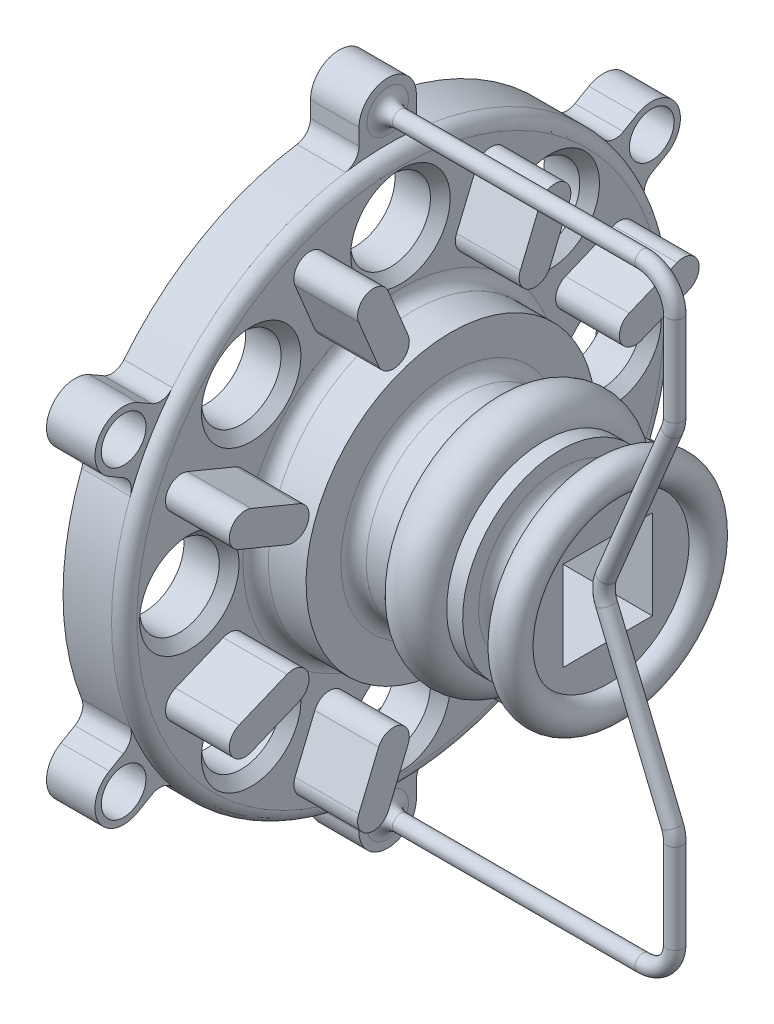
SolidWorks part; units mm, degrees
material "1060 Alloy"
ref_plane "Front Plane" through (0, 0, 0) normal (0, 0, 1) x (1, 0, 0)
ref_plane "Top Plane" through (0, 0, 0) normal (0, 1, 0) x (1, 0, 0)
ref_plane "Right Plane" through (0, 0, 0) normal (1, 0, 0) x (0, 0, -1)
sketch "Sketch1" plane through (0, 0, 0) normal (0, 0, 1) x (1, 0, 0)
  line L0 (0, 24.511) -> (0, 28.829)
  line L1 (0, 28.829) -> (10.033, 28.829)
  line L2 (10.033, 28.829) -> (10.033, 19.3675)
  line L3 (10.033, 19.3675) -> (18.415, 19.3675)
  line L4 (31.75, 19.3675) -> (31.75, 16.1925)
  line L6 (38.1, 16.1925) -> (38.1, 19.3675)
  line L7 (41.275, 16.1925) -> (41.275, 0)
  line L8 (41.275, 0) -> (3.937, 0)
  line L9 (28.575, 19.3675) -> (31.75, 19.3675)
  line L10 (0, 24.511) -> (3.937, 24.511)
  line L11 (3.937, 24.511) -> (3.937, 0)
  line L12 (0, 0) -> (3.937, 0)
  arc A0 (41.275, 16.1925) -> (38.1, 19.3675) centre (41.275, 19.3675) ccw
  arc A1 (31.75, 16.1925) -> (38.1, 16.1925) centre (34.925, 16.1925) ccw
  arc A2 (28.575, 19.3675) -> (18.415, 19.3675) centre (23.495, 19.3675) ccw
  dimension "D1" = 3.175
  dimension "D2" = 41.275
  dimension "D3" = 3.175
  dimension "D7" = 10.16
  dimension "D4" = 6.35
  dimension "D5" = 16.1925
  dimension "D6" = 19.3675
  dimension "D8" = 11.43
  dimension "D9" = 10.033
  dimension "D10" = 28.829
  dimension "D11" = 3.937
  dimension "D12" = 24.511
revolve "Revolve1" add sketch "Sketch1" angle 360 about L8
sketch "Sketch2" plane through (3.937, 0, 0) normal (-1, 0, 0) x (0, 0, 1)
  line L1 (-8.89, 8.89) -> (8.89, 8.89)
  line L2 (-8.89, 8.89) -> (-8.89, -8.89)
  line L3 (-8.89, -8.89) -> (8.89, -8.89)
  line L4 (8.89, 8.89) -> (8.89, -8.89)
  line L5 (-8.89, 8.89) -> (8.89, -8.89) construction
  line L6 (-8.89, -8.89) -> (8.89, 8.89) construction
  point P0 (0, 0)
  dimension "D1" = 17.78
  dimension "D2" = 17.78
extrude "Cut-Extrude2" cut sketch "Sketch2" against normal up to next
sketch "Sketch3" plane through (0, 0, 0) normal (-1, 0, 0) x (0, 0, 1)
  circle A0 centre (0, 0) radius 54.991
  circle A2 centre (0, 0) radius 24.511 construction
  circle A3 centre (0, 0) radius 24.511
  dimension "D1" = 109.982
extrude "Boss-Extrude1" add sketch "Sketch3" along normal blind 12.192
sketch "Sketch5" plane through (-12.192, 0, 0) normal (-1, 0, 0) x (0, 0, 1)
  circle A0 centre (0, 0) radius 51.816
  dimension "D1" = 103.632
extrude "Cut-Extrude4" cut sketch "Sketch5" against normal blind 3.175
chamfer "Chamfer1" distance 6.35 angle 45 1 edges at (-9.017, -24.511, 0)
sketch "Sketch4" plane through (0, 0, 0) normal (1, 0, 0) x (0, 0, -1)
  line L0 (0, 0) -> (54.991, 0) construction
  line L2 (0, 0) -> (29.7246, 29.7246) construction
  circle A0 centre (0, 0) radius 54.991 construction
  circle A1 centre (0, 0) radius 42.037 construction
  circle A2 centre (29.7246, 29.7246) radius 7.9375
  dimension "D3" = 84.074
  dimension "D6" = 15.875
  dimension "D2" = 45
extrude "Cut-Extrude3" cut sketch "Sketch4" against normal up to next
sketch "Sketch6" plane through (0, 0, 0) normal (1, 0, 0) x (0, 0, -1)
  line L0 (0, 0) -> (38.8371, 16.0869) construction
  line L1 (0, 0) -> (42.037, 0) construction
  line L2 (34.0734, 14.1137) -> (43.6008, 18.0601) construction
  line L3 (32.8584, 17.047) -> (42.3858, 20.9934)
  line L4 (35.2884, 11.1804) -> (44.8159, 15.1267)
  circle A0 centre (0, 0) radius 42.037 construction
  arc A1 (32.8584, 17.047) -> (35.2884, 11.1804) centre (34.0734, 14.1137) ccw
  arc A2 (44.8159, 15.1267) -> (42.3858, 20.9934) centre (43.6008, 18.0601) ccw
  point P3 (38.8371, 16.0869)
  dimension "D1" = 84.074
  dimension "D4" = 3.175
  dimension "D2" = 22.5
  dimension "D3" = 5.1562
extrude "Boss-Extrude2" add sketch "Sketch6" along normal blind 12.7
chamfer "Chamfer2" distance 1.9685 angle 45 1 edges at (0, 37.6621, -29.7246)
pattern_circular "CirPattern1" count 8 over 360 about axis through (41.275, 0, 0) along (1, 0, 0) of "Cut-Extrude3", "Boss-Extrude2", "Chamfer2"
sketch "Sketch7" plane through (-12.192, 0, 0) normal (-1, 0, 0) x (0, 0, 1)
  line L0 (5.715, 60.706) -> (5.715, 54.6932)
  line L1 (-5.715, 60.706) -> (-5.715, 54.6932)
  line L2 (0, 60.706) -> (0, 0) construction
  arc A0 (5.715, 60.706) -> (-5.715, 60.706) centre (0, 60.706) ccw
  circle A1 centre (0, 0) radius 54.991 construction
  arc A2 (5.715, 54.6932) -> (-5.715, 54.6932) centre (0, 0) ccw
  dimension "D1" = 60.706
  dimension "D2" = 11.43
  dimension "D3" = 6.0128
extrude "Boss-Extrude3" add sketch "Sketch7" against normal blind 9.652
fillet "Fillet1" radius 3.175 2 edges at (-7.366, 54.6932, -5.715) (-7.366, 54.6932, 5.715)
pattern_circular "CirPattern2" count 6 over 360 about axis through (-12.192, 0, 0) along (1, 0, 0) of "Boss-Extrude3", "Fillet1"
sketch "Sketch8" plane through (-12.192, 0, 0) normal (-1, 0, 0) x (0, 0, 1)
  circle A0 centre (52.5729, 30.353) radius 4.445
  circle A1 centre (52.5729, -30.353) radius 4.445
  circle A2 centre (-52.5729, -30.353) radius 4.445
  circle A3 centre (-52.5729, 30.353) radius 4.445
  dimension "D1" = 8.89
extrude "Cut-Extrude5" cut sketch "Sketch8" against normal blind 9.652
sketch "Sketch9" plane through (0, 0, 0) normal (0, 0, 1) x (1, 0, 0)
  line L0 (-2.54, 60.706) -> (48.26, 60.706)
  line L1 (54.61, 54.356) -> (54.61, 36.5676)
  line L2 (54.1278, 34.1402) -> (41.0091, 2.4273)
  line L3 (41.0091, -2.4273) -> (54.1278, -34.1402)
  line L4 (54.61, -36.5676) -> (54.61, -54.356)
  line L5 (48.26, -60.706) -> (-2.54, -60.706)
  line L6 (-12.192, 66.421) -> (-12.192, 60.706) construction
  line L7 (0, 0) -> (40.005, 0) construction
  arc A0 (54.61, 36.5676) -> (54.1278, 34.1402) centre (48.26, 36.5676) cw
  arc A1 (54.1278, -34.1402) -> (54.61, -36.5676) centre (48.26, -36.5676) cw
  arc A2 (41.0091, 2.4273) -> (41.0091, -2.4273) centre (46.8769, 0) ccw
  arc A3 (54.61, -54.356) -> (48.26, -60.706) centre (48.26, -54.356) cw
  arc A4 (48.26, 60.706) -> (54.61, 54.356) centre (48.26, 54.356) cw
  point P15 (54.61, 35.306)
  point P18 (54.61, -35.306)
  point P24 (54.61, -60.706)
  point P27 (54.61, 60.706)
  dimension "D5" = 6.35
  dimension "D1" = 66.802
  dimension "D2" = 25.4
  dimension "D3" = 25.4
  dimension "D4" = 14.605
sketch "Sketch10" plane through (-2.54, 0, 0) normal (1, 0, 0) x (0, 0, -1)
  line L0 (0, 54.356) -> (0, 36.5676) construction
  circle A0 centre (0, 60.706) radius 1.5875
  dimension "D1" = 3.175
sweep "Sweep1" add profiles "Sketch10" path "Sketch9"
fillet "Fillet2" radius 2.54 6 edges at (3.937, 24.511, 0) (10.033, 19.3675, 0) (0, 28.829, 0) (0, -54.991, 0) (-2.54, -62.2935, 0) (-2.54, 62.2935, 0)
